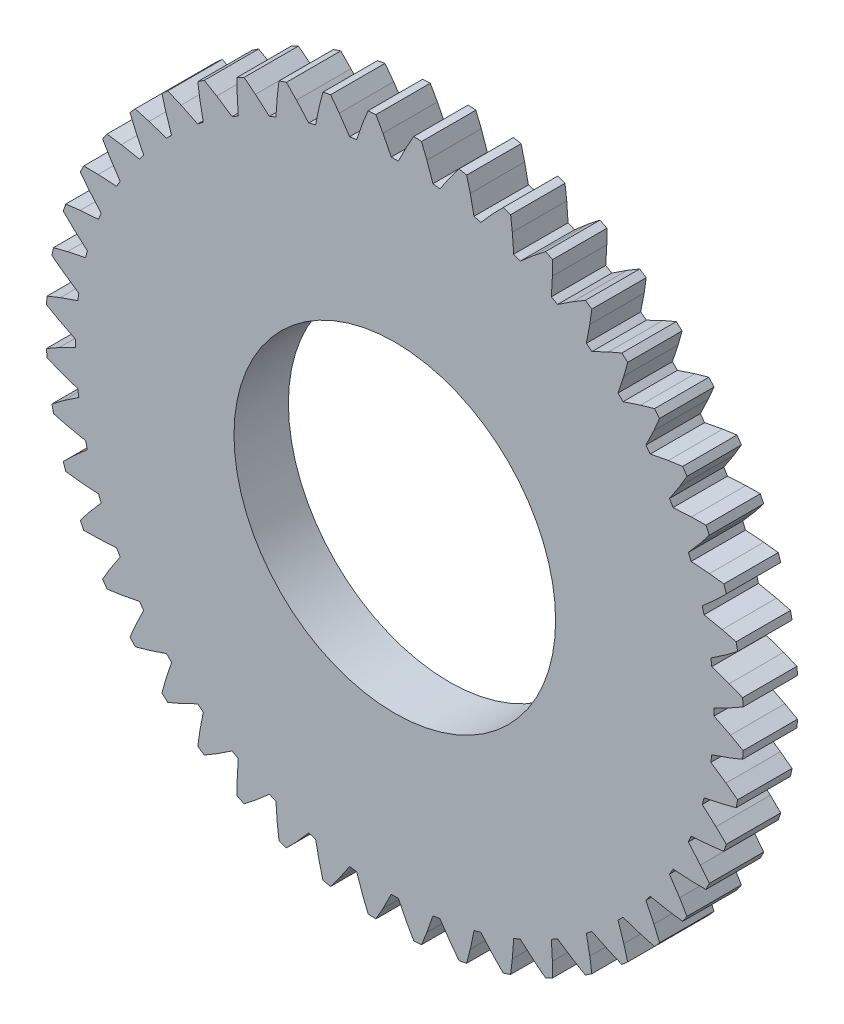
SolidWorks part; units mm, degrees
material "Latón de decoletaje, UNS C36000"
ref_plane "Alzado" through (0, 0, 0) normal (0, 0, 1) x (1, 0, 0)
ref_plane "Planta" through (0, 0, 0) normal (0, 1, 0) x (1, 0, 0)
ref_plane "Vista lateral" through (0, 0, 0) normal (1, 0, 0) x (0, 0, -1)
sketch "Croquis1" plane through (0, 0, 0) normal (0, 0, 1) x (1, 0, 0)
  circle A0 centre (0, 0) radius 7.375
  dimension "D1" = 14.75
extrude "Saliente-Extruir1" add sketch "Croquis1" along normal blind 1.15
sketch "Croquis2" plane through (0, 0, 1.15) normal (0, 0, 1) x (1, 0, 0)
  line L0 (0, 0) -> (0, 11.4845) construction
  line L1 (0.4764, 7.5) -> (-0.4764, 7.5)
  line L2 (-0.4764, 7.5) -> (-0.4, 7.3641)
  line L3 (-0.4, 7.3641) -> (-0.25, 7.0974)
  line L4 (-0.25, 7.0974) -> (-0.075, 6.7496)
  line L5 (0.4764, 7.5) -> (0.4, 7.3641)
  line L6 (0.4, 7.3641) -> (0.25, 7.0974)
  line L7 (0.25, 7.0974) -> (0.075, 6.7496)
  circle A0 centre (0, 0) radius 6.75
  circle A1 centre (0, 0) radius 7.375 construction
  circle A2 centre (0, 0) radius 3.4
  point P14 (0, 7.5)
  dimension "D1" = 13.5
  dimension "D4" = 0.25
  dimension "D5" = 7.5
  dimension "D7" = 6.8
  dimension "D2" = 0.4
  dimension "D3" = 0.075
  dimension "D6" = 7.0974
extrude "Cortar-Extruir1" cut sketch "Croquis2" against normal blind 1.3 contours L0 A0 L7 L6 L2 | A0 L0 L2 L3 L4 region at (-0.1601, 7.2179, 1.15) region at (0.1601, 7.2179, 1.15)
pattern_circular "MatrizC1" count 48 over 360 about axis through (0, 0, 1.15) along (0, 0, -1) of "Cortar-Extruir1"
extrude "Cortar-Extruir2" cut sketch "Croquis2<3>" against normal blind 2.1 contours A2 region at (0, 0, 1.15)
sketch "Croquis2<3>" plane through (0, 0, 1.15) normal (0, 0, 1) x (1, 0, 0) same geometry as "Croquis2"
